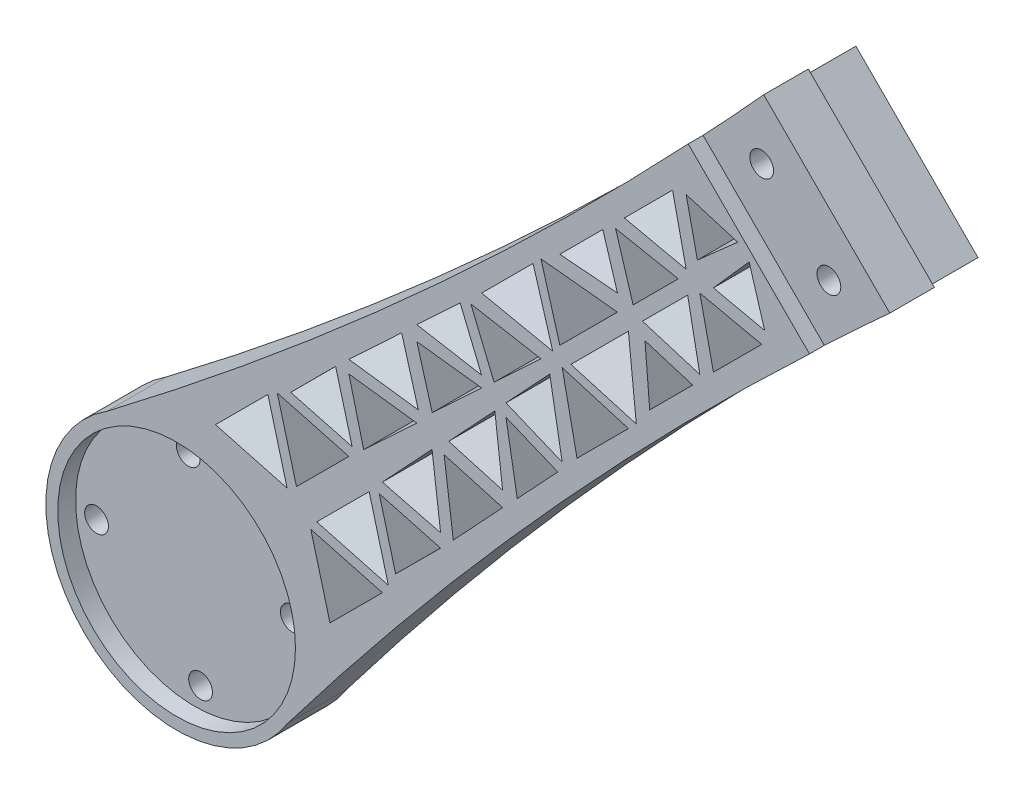
SolidWorks part; units mm, degrees
material "PBT General Purpose"
ref_plane "Front Plane" through (0, 0, 0) normal (0, 0, 1) x (1, 0, 0)
ref_plane "Top Plane" through (0, 0, 0) normal (0, 1, 0) x (1, 0, 0)
ref_plane "Right Plane" through (0, 0, 0) normal (1, 0, 0) x (0, 0, -1)
sketch "Sketch1" plane through (0, 0, 0) normal (0, 0, 1) x (1, 0, 0)
  line L0 (-53.7252, -32.512) -> (-32.512, -53.7252)
  line L1 (-135, -150) -> (150, -150) construction
  line L2 (-150, -150) -> (-150, 150) construction
  line L3 (-150, 150) -> (150, 150) construction
  line L4 (150, -150) -> (150, 150) construction
  line L5 (-150, -150) -> (150, 150) construction
  line L6 (-150, 150) -> (150, -150) construction
  line L7 (-50, 50) -> (50, 50) construction
  line L8 (-50, 50) -> (-50, -50) construction
  line L9 (-50, -50) -> (50, -50) construction
  line L10 (50, 50) -> (50, -50) construction
  line L11 (-50, 50) -> (50, -50) construction
  line L12 (-50, -50) -> (50, 50) construction
  arc A0 (-161.7567, -131.4048) -> (-131.4048, -161.7567) centre (-150, -150) ccw
  arc A1 (-53.7252, -32.512) -> (-161.7567, -131.4048) centre (-645.6489, 505.6574) cw
  arc A2 (-32.512, -53.7252) -> (-131.4048, -161.7567) centre (505.6574, -645.6489) ccw
  point P0 (0, 0)
  point P6 (0, 0)
  point P14 (-43.1186, -43.1186)
  dimension "D5" = 44
  dimension "D6" = 800
  dimension "D1" = 300
  dimension "D2" = 300
  dimension "D3" = 100
  dimension "D4" = 30
  dimension "D7" = 53.7252
  dimension "D8" = 53.7252
extrude "Boss-Extrude1" add sketch "Sketch1" along normal blind 10
sketch "Sketch3" plane through (0, 0, 10) normal (0, 0, 1) x (1, 0, 0)
  line L0 (-165.5563, -165.5563) -> (-43.1186, -43.1186)
  line L1 (-32.512, -53.7252) -> (-53.7252, -32.512) construction
  arc A0 (-161.7567, -131.4048) -> (-131.4048, -161.7567) centre (-150, -150) ccw construction
ref_plane "Plane1" through (0, 0, 0) normal (0.7071, -0.7071, 0) x (0.7071, 0.7071, 0)
sketch "Sketch4" plane through (0, 0, 0) normal (0.7071, -0.7071, 0) x (0.7071, 0.7071, 0)
  line L0 (-225.5314, 0) -> (-221.9919, -13.748)
  line L1 (-234.132, 0) -> (-207.2965, 0) construction
  line L2 (-219.0866, -16) -> (-215.412, -16)
  line L3 (-215.412, -16) -> (-215.412, 0)
  line L4 (-215.412, 0) -> (-225.5314, 0)
  arc A0 (-221.9919, -13.748) -> (-219.0866, -16) centre (-219.0866, -13) ccw
  point P9 (-221.412, -16)
  dimension "D3" = 3
  dimension "D1" = 16
  dimension "D2" = 6
extrude "Boss-Extrude2" add sketch "Sketch4" along normal mid plane 10 separate body
sketch "Sketch5" plane through (0, 0, 10) normal (0, 0, 1) x (1, 0, 0)
  circle A0 centre (-150, -150) radius 20
  dimension "D1" = 40
extrude "Cut-Extrude1" cut sketch "Sketch5" against normal blind 3
sketch "Sketch7" plane through (0, 0, 7) normal (0, 0, 1) x (1, 0, 0)
  line L0 (-170.1559, -132.2305) -> (-150, -150) construction
  line L1 (-166.4674, -151.0362) -> (-150, -150) construction
  circle A0 centre (-166.4674, -151.0362) radius 2
  circle A1 centre (-151.0362, -133.5326) radius 2
  circle A2 centre (-133.5326, -148.9638) radius 2
  circle A3 centre (-148.9638, -166.4674) radius 2
  circle A4 centre (-150, -150) radius 16.5 construction
  point P14 (-150, -150)
  dimension "D3" = 4
  dimension "D4" = 33
  dimension "D1" = 45
  dimension "D2" = 4
extrude "Cut-Extrude2" cut sketch "Sketch7" against normal through all
sketch "Sketch8" plane through (0, 0, 10) normal (0, 0, 1) x (1, 0, 0)
  line L0 (-63.927, -43.5234) -> (-43.5234, -63.927)
  line L1 (-32.512, -53.7252) -> (-53.7252, -32.512)
  line L2 (-32.512, -53.7252) -> (-53.7252, -32.512)
  arc A3 (-161.7567, -131.4048) -> (-131.4048, -161.7567) centre (-150, -150) ccw
  arc A4 (-32.512, -53.7252) -> (-131.4048, -161.7567) centre (505.6574, -645.6489) ccw
  arc A5 (-161.7567, -131.4048) -> (-53.7252, -32.512) centre (-645.6489, 505.6574) ccw
  arc A6 (-161.7567, -131.4048) -> (-131.4048, -161.7567) centre (-150, -150) ccw
  arc A7 (-32.512, -53.7252) -> (-131.4048, -161.7567) centre (505.6574, -645.6489) ccw
  arc A8 (-161.7567, -131.4048) -> (-53.7252, -32.512) centre (-645.6489, 505.6574) ccw
  arc M7 (-53.7252, -32.512) -> (-161.7567, -131.4048) centre (-645.6489, 505.6574) cw
  arc M9 (-131.4048, -161.7567) -> (-32.512, -53.7252) centre (505.6574, -645.6489) cw
  line M10 (-32.512, -53.7252) -> (-53.7252, -32.512)
  dimension "D2" = 15
  dimension "D1" = 0
extrude "Cut-Extrude3" cut sketch "Sketch8" against normal blind 2.5 contours L0 M7 M9 M10 region at (-48.3874, -48.3874, 10)
sketch "Sketch9" plane through (0, 0, 7.5) normal (0, 0, 1) x (1, 0, 0)
  line L0 (-58.8002, -38.0416) -> (-38.0416, -58.8002) construction
  line L1 (-53.7252, -53.7252) -> (-34.3472, -34.3472) construction
  line L2 (-63.927, -43.5234) -> (-43.5234, -63.927) construction
  line L3 (-64.6184, -64.6184) -> (64.6184, 64.6184) construction
  arc A0 (-63.927, -43.5234) -> (-53.7252, -32.512) centre (-645.6489, 505.6574) ccw construction
  arc A1 (-32.512, -53.7252) -> (-43.5234, -63.927) centre (505.6574, -645.6489) ccw construction
  circle A2 centre (-54.0778, -42.7641) radius 2
  circle A3 centre (-42.7641, -54.0778) radius 2
  dimension "D1" = 4
  dimension "D2" = 8
extrude "Cut-Extrude4" cut sketch "Sketch9" against normal through all
sketch "Sketch10" plane through (0, 0, 0) normal (0.7071, -0.7071, 0) x (0.7071, 0.7071, 0)
  line L0 (-207.2965, 0) -> (-60.9789, 0) construction
  line L1 (-77.7626, 0) -> (-72.7626, 0)
  line L2 (-77.7626, 0) -> (-77.7626, -16)
  line L3 (-77.7626, -16) -> (-72.7626, -16)
  line L4 (-72.7626, 0) -> (-72.7626, -16)
  line L5 (-219.0866, -16) -> (-215.412, -16) construction
  dimension "D1" = 5
extrude "Boss-Extrude3" add sketch "Sketch10" along normal up to surface and the other way up to surface separate body up to face at (-69.8992, -92.4525, 5.8333) other way up to face at (-92.4525, -69.8992, 5.8333)
ref_axis "Axis1" through (-54.0778, -42.7641, 0) along (0, 0, 1)
sketch "Sketch11" plane through (0, 0, 10) normal (0, 0, 1) x (1, 0, 0)
  line L0 (-165.5563, -165.5563) -> (-24.8411, -24.8411) construction
  line L1 (-133.0637, -114.3791) -> (-129.8369, -126.4215)
  line L2 (-131.4127, -127.4254) -> (-134.6395, -115.383)
  line L3 (-134.6395, -115.383) -> (-143.4552, -124.1987)
  line L4 (-143.4552, -124.1987) -> (-131.4127, -127.4254)
  line L5 (-121.0213, -117.6059) -> (-133.0637, -114.3791)
  line L6 (-129.8369, -126.4215) -> (-121.0213, -117.6059)
  line L7 (-121.0213, -105.5883) -> (-118.5291, -115.383)
  line L8 (-123.2498, -105.5883) -> (-130.7977, -113.157)
  line L9 (-130.7977, -113.157) -> (-120.4691, -115.9093)
  line L10 (-120.4691, -115.9093) -> (-123.2498, -105.5883)
  line L11 (-118.5291, -115.383) -> (-109.5902, -107.0295)
  line L12 (-109.5902, -107.0295) -> (-121.0213, -105.5883)
  line L13 (-121.0213, -103.454) -> (-112.1406, -95.1548)
  line L14 (-112.1406, -95.1548) -> (-109.3336, -104.9943)
  line L15 (-109.3336, -104.9943) -> (-121.0213, -103.454)
  line L16 (-109.5902, -95.1548) -> (-107.003, -104.2241)
  line L17 (-107.003, -104.2241) -> (-98.6973, -96.4623)
  line L18 (-98.6973, -96.4623) -> (-109.5902, -95.1548)
  line L19 (-109.5902, -92.6906) -> (-102.2987, -85.8766)
  line L20 (-102.2987, -85.8766) -> (-98.6973, -94.5925)
  line L21 (-98.6973, -94.5925) -> (-109.5902, -92.6906)
  line L22 (-97.8633, -81.8179) -> (-90.0356, -73.9902)
  line L23 (-100.498, -85.1325) -> (-96.5891, -94.5925)
  line L24 (-96.5891, -94.5925) -> (-88.7053, -87.225)
  line L25 (-88.7053, -87.225) -> (-100.498, -85.1325)
  line L26 (-90.0356, -73.9902) -> (-86.721, -85.1325)
  line L27 (-86.721, -85.1325) -> (-98.6973, -82.631)
  line L28 (-98.6973, -82.631) -> (-97.8633, -81.8179)
  line L29 (-88.7053, -72.6635) -> (-85.5247, -83.6754)
  line L30 (-85.5247, -83.6754) -> (-75.8396, -73.9902)
  line L31 (-75.8396, -73.9902) -> (-88.7053, -72.6635)
  line L32 (-85.5247, -70.408) -> (-78.294, -63.1774)
  line L33 (-78.294, -63.1774) -> (-75.8396, -71.2041)
  line L34 (-75.8396, -71.2041) -> (-85.5247, -70.408)
  line L35 (-76.1514, -61.9744) -> (-73.2003, -71.6256)
  line L36 (-73.2003, -71.6256) -> (-65.5991, -64.0245)
  line L37 (-65.5991, -64.0245) -> (-76.1514, -61.9744)
  line L38 (-74.6758, -59.6884) -> (-66.5634, -51.576)
  line L39 (-66.5634, -51.576) -> (-64.2774, -61.9744)
  line L40 (-64.2774, -61.9744) -> (-74.6758, -59.6884)
  line L41 (-64.2774, -51.0734) -> (-62.3834, -59.6884)
  line L42 (-62.3834, -59.6884) -> (-55.5932, -53.6799)
  line L43 (-55.5932, -53.6799) -> (-64.2774, -51.0734)
  arc A0 (-161.7567, -131.4048) -> (-131.4048, -161.7567) centre (-150, -150) ccw construction
  circle A1 centre (-136.5025, -122.3357) radius 3.599 construction
  circle A2 centre (-124.8388, -111.5515) radius 2.0421 construction
extrude "Cut-Extrude5" cut sketch "Sketch11" against normal through all
ref_plane "Plane2" through (0, 0, 0) normal (-0.7071, 0.7071, 0) x (0.7071, 0.7071, 0)
mirror "Mirror1" about plane through (0, 0, 0) normal (-0.7071, 0.7071, 0) of "Cut-Extrude5"
